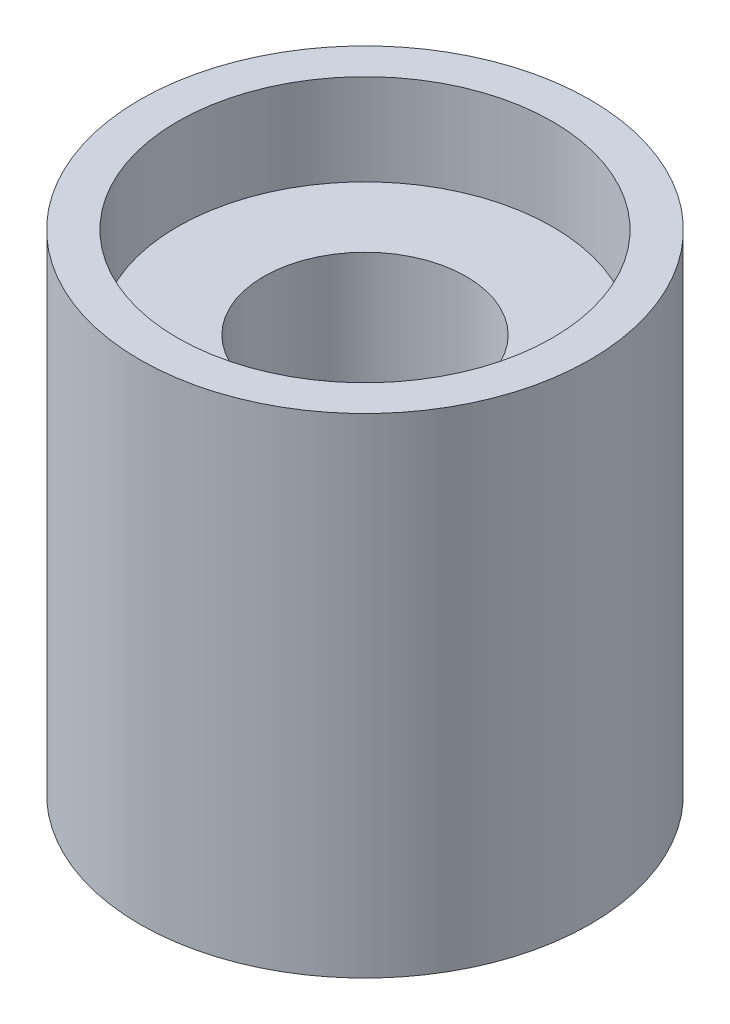
SolidWorks part; units mm, degrees
ref_plane "Front Plane" through (0, 0, 0) normal (0, 0, 1) x (1, 0, 0)
ref_plane "Top Plane" through (0, 0, 0) normal (0, 1, 0) x (1, 0, 0)
ref_plane "Right Plane" through (0, 0, 0) normal (1, 0, 0) x (0, 0, -1)
sketch "Sketch1" plane through (0, 0, 0) normal (0, 1, 0) x (1, 0, 0)
  circle A0 centre (0, 0) radius 22.225
  dimension "D1" = 44.45
extrude "Boss-Extrude1" add sketch "Sketch1" along normal blind 48.26
sketch "Sketch2" plane through (0, 48.26, 0) normal (0, 1, 0) x (1, 0, 0)
  circle A0 centre (0, 0) radius 18.5039
  dimension "D1" = 37.0078
extrude "Cut-Extrude1" cut sketch "Sketch2" against normal blind 8.9916
sketch "Sketch4" plane through (0, 0, 0) normal (0, -1, 0) x (1, 0, 0)
  circle A0 centre (0, 0) radius 18.5039
  dimension "D1" = 37.0078
extrude "Cut-Extrude2" cut sketch "Sketch4" against normal blind 8.9916
sketch "Sketch5" plane through (0, 8.9916, 0) normal (0, -1, 0) x (1, 0, 0)
  circle A0 centre (0, 0) radius 9.9949
  dimension "D1" = 19.9898
extrude "Cut-Extrude3" cut sketch "Sketch5" against normal through all
